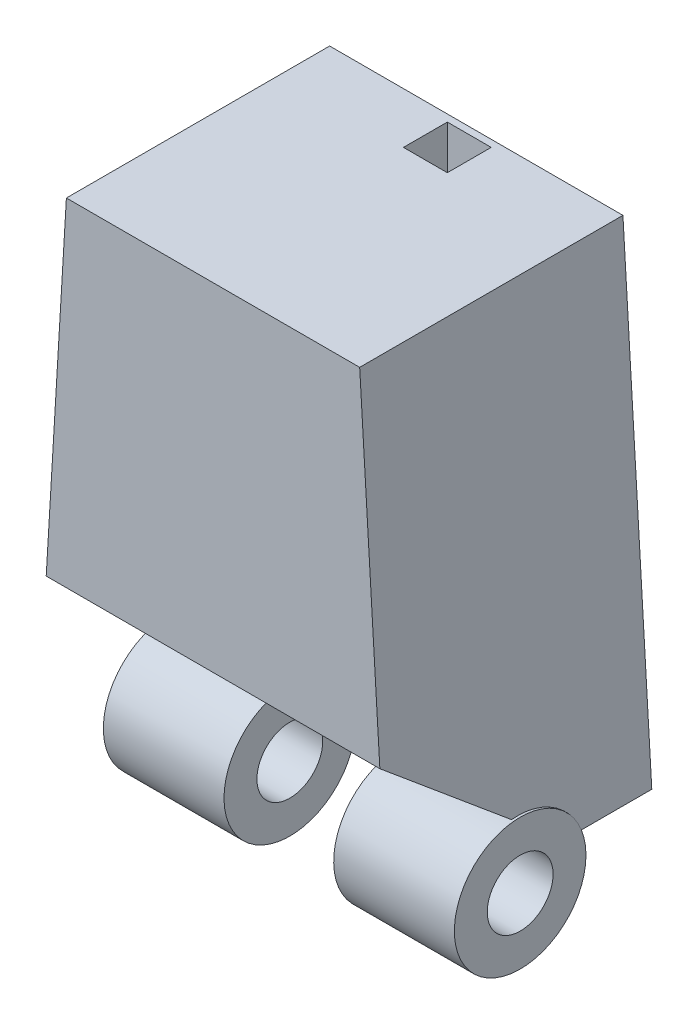
SolidWorks part; units mm, degrees
ref_plane "Front Plane" through (0, 0, 0) normal (0, 0, 1) x (1, 0, 0)
ref_plane "Top Plane" through (0, 0, 0) normal (0, 1, 0) x (1, 0, 0)
ref_plane "Right Plane" through (0, 0, 0) normal (1, 0, 0) x (0, 0, -1)
sketch "Sketch1" plane through (0, 0, 0) normal (0, 0, 1) x (1, 0, 0)
  line L0 (-56.5743, 0) -> (-40.5743, 0)
  line L2 (-56.5743, 0) -> (-55.2587, 22)
  line L3 (-40.5743, 0) -> (-41.8899, 22)
  arc A0 (-41.8899, 22) -> (-55.2587, 22) centre (-48.5743, 22) ccw
extrude "Boss-Extrude1" add sketch "Sketch1" along normal blind 12
sketch "Sketch2" plane through (0, 0, 12) normal (0, 0, 1) x (1, 0, 0)
  line L0 (-40.5743, 0) -> (-56.5743, 0)
  line L1 (-48.5743, 0) -> (-48.5743, 29.5391)
ref_plane "Plane1" through (-48.5743, 0, 0) normal (1, 0, 0) x (0, 0, -1)
sketch "Sketch3" plane through (-48.5743, 0, 0) normal (1, 0, 0) x (0, 0, -1)
  line L0 (0, 0) -> (-4, 0)
  line L1 (-12, 0) -> (0, 0) construction
  line L2 (-4, 0) -> (-12, 6.614)
  line L3 (-12, 0) -> (-12, 22) construction
  line L4 (-12, 6.614) -> (-12, 0)
  line L5 (-12, 0) -> (-4, 0)
extrude "Cut-Extrude1" cut sketch "Sketch3" against normal through all both and the other way through all contours L4 L5 L2 region at (-48.5743, 2.2047, 9.3333)
sketch "Sketch6" plane through (-48.5743, 0, 0) normal (1, 0, 0) x (0, 0, -1)
  line L1 (0, 0) -> (-12, 0)
  line L2 (-6, 0) -> (-6, -1.1)
  circle A0 centre (-6, -1.1) radius 1.5
  circle A1 centre (-6, -1.1) radius 3
extrude "Boss-Extrude2" add sketch "Sketch6" along normal mid plane 16 contours L1 A1 A0 | L1 A1 A0 region at (-48.5743, -0.5537, 3.1241) region at (-48.5743, 0.8343, 6)
extrude "Cut-Extrude2" cut sketch "Sketch6<3>" against normal mid plane 5 contours L1 A1 A0 | L1 A1 A0 region at (-48.5743, -0.5537, 3.1241) region at (-48.5743, 0.8343, 6)
sketch "Sketch6<3>" plane through (-48.5743, 0, 0) normal (1, 0, 0) x (0, 0, -1) same geometry as "Sketch6"
sketch "Sketch7" plane through (-48.5743, 0, 0) normal (1, 0, 0) x (0, 0, -1)
  line L0 (-7.1617, 2.6139) -> (-11.0152, 5.7998)
  line L1 (-6.2821, 1.8867) -> (-12, 6.614) construction
  line L2 (-7.1617, 2.6139) -> (-3.9757, 6.4674)
  line L3 (-3.9757, 6.4674) -> (-7.8293, 9.6534)
  line L4 (-7.8293, 9.6534) -> (-11.0152, 5.7998)
  line L5 (-12, 6.614) -> (-6.2821, 1.8867) construction
extrude "Cut-Extrude3" cut sketch "Sketch7" against normal mid plane 10
sketch "Sketch8" plane through (-48.5743, 0, 0) normal (1, 0, 0) x (0, 0, -1)
  circle A0 centre (-7.5481, 6.1771) radius 1.5
extrude "Boss-Extrude3" add sketch "Sketch8" along normal mid plane 11
sketch "Sketch9" plane through (-48.5743, 0, 0) normal (1, 0, 0) x (0, 0, -1)
  line L1 (-12, 28.6844) -> (0, 28.6844)
  line L2 (-12, 28.6844) -> (-12, 22)
  line L3 (-12, 22) -> (0, 22)
  line L4 (0, 28.6844) -> (0, 22)
extrude "Cut-Extrude4" cut sketch "Sketch9" against normal through all both and the other way through all
sketch "Sketch11" plane through (-48.5743, 0, 0) normal (1, 0, 0) x (0, 0, -1)
  line L0 (-0.32, 22) -> (-2.32, 22)
  line L2 (-12, 22) -> (0, 22) construction
  line L3 (-2.32, 22) -> (-2.32, 20.5436)
  line L5 (-0.32, 20.5436) -> (-0.32, 22)
  line L6 (-2.32, 20.5436) -> (-2.32, -1.5624)
  line L7 (-2.32, -1.5624) -> (-0.32, -1.5624)
  line L8 (-0.32, -1.5624) -> (-0.32, 20.5436)
extrude "Cut-Extrude5" cut sketch "Sketch11" against normal mid plane 2
